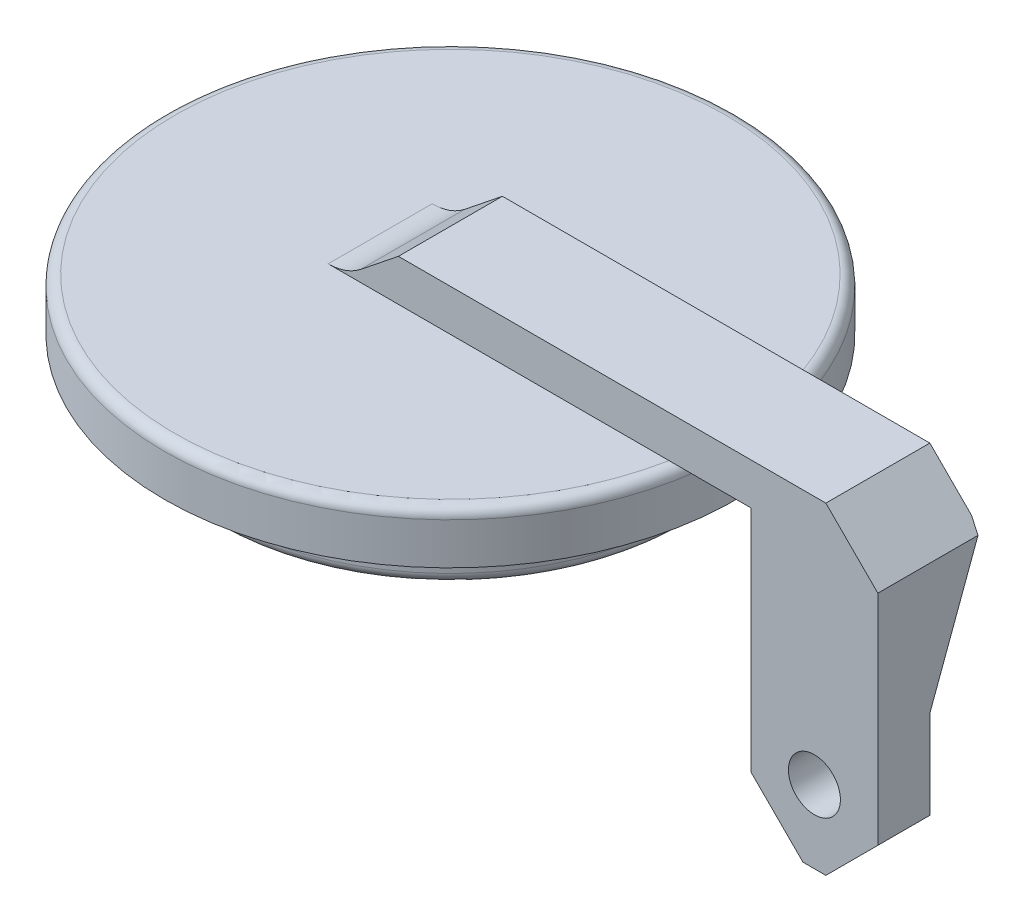
SolidWorks part; units mm, degrees
ref_plane "Front Plane" through (0, 0, 0) normal (0, 0, 1) x (1, 0, 0)
ref_plane "Top Plane" through (0, 0, 0) normal (0, 1, 0) x (1, 0, 0)
ref_plane "Right Plane" through (0, 0, 0) normal (1, 0, 0) x (0, 0, -1)
sketch "Sketch2" plane through (0, 0, 0) normal (0, 0, 1) x (1, 0, 0)
  line L0 (0, 0) -> (22.5, 0)
  line L1 (22.5, 0) -> (22.5, 5)
  line L2 (22.5, 5) -> (27.5, 5)
  line L3 (27.5, 5) -> (27.5, 10)
  line L4 (27.5, 10) -> (0, 10)
  line L5 (0, 10) -> (0, 0)
  dimension "D1" = 22.5
  dimension "D2" = 5
  dimension "D3" = 5
  dimension "D4" = 5
revolve "Revolve1" add sketch "Sketch2" angle 360 about L5
fillet "Fillet1" radius 1 3 edges at (0, 10, 27.5) (0, 5, 22.5) (0, 0, 22.5)
sketch "Sketch5" plane through (0, 0, 0) normal (0, 0, 1) x (1, 0, 0)
  line L4 (0, 10) -> (46.1, 10)
  line L5 (26.5, 10) -> (-26.5, 10) construction
  line L6 (0, 14) -> (46.1, 14)
  line L7 (46.1, 14) -> (46.1, 10)
  line L8 (0, 10) -> (-5, 10)
  line L9 (-5, 10) -> (0, 14)
  dimension "D3" = 5
  dimension "D1" = 46.1
  dimension "D2" = 4
  dimension "D4" = 6.4031
extrude "Boss-Extrude2" add sketch "Sketch5" along normal mid plane 10
sketch "Sketch14" plane through (0, 0, 0) normal (0, 0, 1) x (1, 0, 0)
  line L5 (46.1, 10) -> (33.9, 10)
  line L6 (26.024, 10) -> (46.1, 10) construction
  line L7 (33.9, 10) -> (33.9, -17)
  line L8 (33.9, -17) -> (46.1, -17)
  line L9 (46.1, -17) -> (46.1, 10)
  line L10 (40, -17) -> (40, -10) construction
  circle A0 centre (40, -10) radius 2.5
  dimension "D2" = 5
  dimension "D1" = 7
  dimension "D3" = 12.2
  dimension "D4" = 27
extrude "Boss-Extrude6" add sketch "Sketch14" along normal blind 5
sketch "Sketch15" plane through (46.1, 0, 0) normal (1, 0, 0) x (0, 0, -1)
  line L0 (5, 10) -> (0, -3.5)
  line L1 (0, -17) -> (0, 10) construction
  line L2 (5, 10) -> (0, 10)
  line L3 (0, 10) -> (0, -3.5)
extrude "Boss-Extrude7" add sketch "Sketch15" against normal blind 12.2
fillet "Fillet2" radius 5 1 edges at (-5, 10, 0)
chamfer "Chamfer1" distance 5 angle 45 3 edges at (46.1, 14, 0) (33.9, -17, 2.5) (46.1, -17, 2.5)
